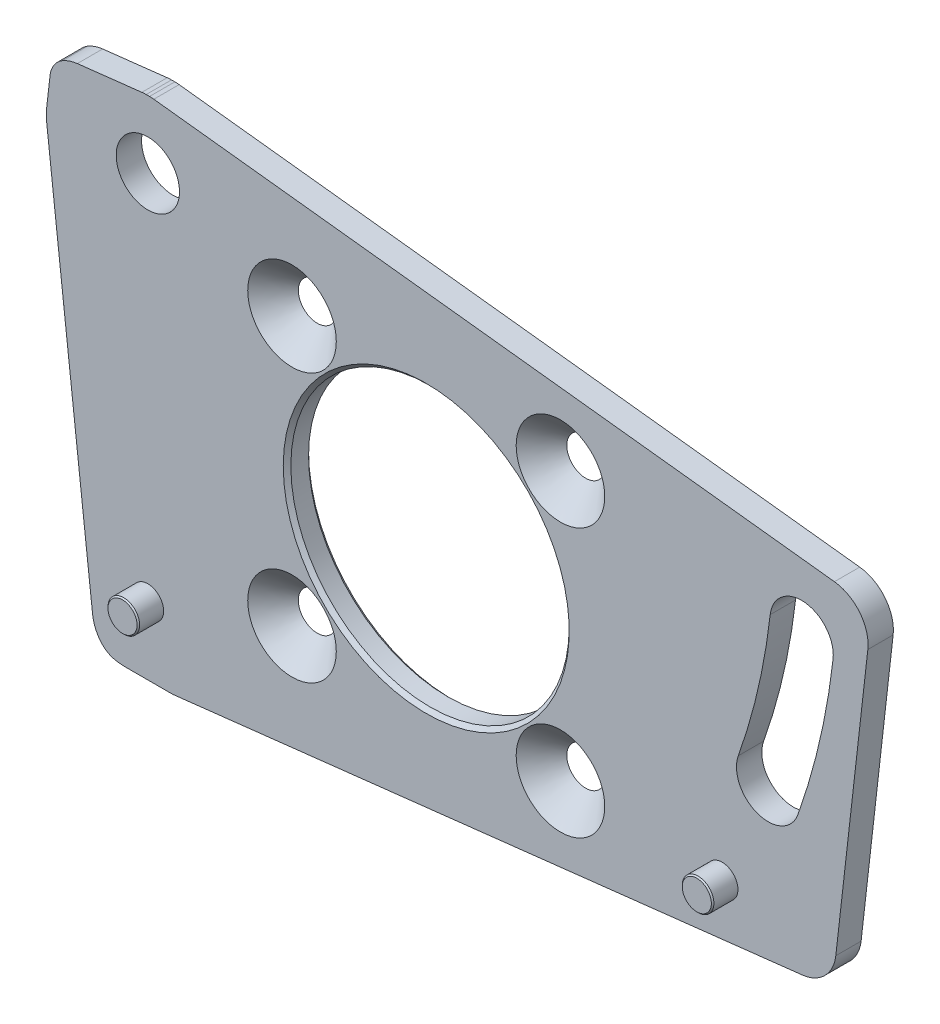
SolidWorks part; units mm, degrees
ref_plane "Płaszczyzna przednia" through (0, 0, 0) normal (0, 0, 1) x (1, 0, 0)
ref_plane "Płaszczyzna górna" through (0, 0, 0) normal (0, 1, 0) x (1, 0, 0)
ref_plane "Płaszczyzna prawa" through (0, 0, 0) normal (1, 0, 0) x (0, 0, -1)
sketch "Szkic1" plane through (0, 0, 0) normal (0, 0, 1) x (1, 0, 0)
  line L0 (0, 0) -> (-23.297, 23.297) construction
  line L1 (-27, -20) -> (27, -20)
  line L2 (-30, -17) -> (-30, 17)
  line L3 (-27, 20) -> (27, 20)
  line L4 (30, -17) -> (30, 17)
  line L5 (-30, -20) -> (30, 20) construction
  line L6 (-30, 20) -> (30, -20) construction
  line L7 (0, 0) -> (25.2349, 25.2349) construction
  arc A0 (27, 20) -> (30, 17) centre (27, 17) cw
  arc A1 (27, -20) -> (30, -17) centre (27, -17) ccw
  arc A2 (-27, -20) -> (-30, -17) centre (-27, -17) cw
  arc A3 (-30, 17) -> (-27, 20) centre (-27, 17) cw
  circle A4 centre (0, 0) radius 11
  circle A5 centre (-22, 14.6667) radius 2.5
  circle A8 centre (-10.6066, -10.6066) radius 1.5
  circle A9 centre (10.6066, -10.6066) radius 1.5
  circle A10 centre (10.6066, 10.6066) radius 1.5
  circle A11 centre (-10.6066, 10.6066) radius 1.5
  circle A12 centre (0, 0) radius 15 construction
  point P0 (0, 0)
  dimension "D3" = 3
  dimension "D4" = 30
  dimension "D6" = 3
  dimension "D7" = 3
  dimension "D8" = 3
  dimension "D9" = 3
  dimension "D10" = 22
  dimension "D11" = 5
  dimension "D1" = 60
  dimension "D2" = 40
  dimension "D5" = 45
  dimension "D12" = 8
extrude "Dodanie-wyciągnięcie1" add sketch "Szkic1" along normal blind 2
chamfer "Sfazowanie1" distance 0.3 angle 45 2 edges at (11, 0, 0) (11, 0, 2)
chamfer "Sfazowanie2" distance 2 angle 45 4 edges at (-9.1066, -10.6066, 2) (12.1066, -10.6066, 2) (12.1066, 10.6066, 2) (-9.1066, 10.6066, 2)
sketch "Szkic2" plane through (0, 0, 2) normal (0, 0, 1) x (1, 0, 0)
  line L9 (26.0813, 25.5127) -> (-27.5716, 19.3997)
  line L10 (-30.2127, 16.0794) -> (-26.3638, -17.7021)
  line L11 (-23.0435, -20.3432) -> (30.6094, -14.2302)
  line L12 (33.2505, -10.9099) -> (29.4016, 22.8716)
  arc A8 (29.4016, 22.8716) -> (26.0813, 25.5127) centre (26.4209, 22.532) ccw
  arc A9 (-27.5716, 19.3997) -> (-30.2127, 16.0794) centre (-27.232, 16.419) ccw
  arc A10 (-26.3638, -17.7021) -> (-23.0435, -20.3432) centre (-23.3831, -17.3625) ccw
  arc A11 (30.6094, -14.2302) -> (33.2505, -10.9099) centre (30.2698, -11.2495) ccw
sketch "Szkic3" plane through (0, 0, 0) normal (0, 0, 1) x (1, 0, 0)
  line L0 (-22, 14.6667) -> (-22, -14.6667) construction
  line L1 (25.8424, 10.5577) -> (-22, 14.6667) construction
  line L2 (-22, 14.6667) -> (23.383, -11.0277) construction
  line L3 (26, 16) -> (-22, 14.6667) construction
  line L4 (-22, 14.6667) -> (25.0697, 5.1682) construction
  line L5 (26, -5.725) -> (-22, 14.6667) construction
  line L6 (-22, 14.6667) -> (20.1826, -16) construction
  line L7 (-18.6794, -14.4781) -> (-22, 14.6667) construction
  line L8 (-22, 14.6667) -> (-25.3206, -14.4781) construction
  line L9 (-30, 17) -> (-30, -17) construction
  line L10 (-27, -20) -> (27, -20) construction
  line L11 (-27, -20) -> (27, -20) construction
  line L12 (30, -17) -> (30, 17) construction
  line L14 (27, 20) -> (-27, 20) construction
  line L15 (30, -17) -> (30, 17) construction
  circle A3 centre (-22, 14.6667) radius 29.3333 construction
  circle A4 centre (-22, 14.6667) radius 52.1519 construction
  arc A9 (-18.5379, -15.7201) -> (-18.8209, -13.2361) centre (-18.6794, -14.4781) ccw construction
  arc A10 (-25.4621, -15.7201) -> (-18.5379, -15.7201) centre (-22, 14.6667) ccw construction
  arc A11 (-25.1791, -13.2361) -> (-25.4621, -15.7201) centre (-25.3206, -14.4781) ccw construction
  arc A12 (-25.1791, -13.2361) -> (-18.8209, -13.2361) centre (-22, 14.6667) ccw construction
  circle A13 centre (-22, 14.6667) radius 48.0185 construction
  arc A18 (27.1505, -6.2137) -> (24.8495, -5.2362) centre (26, -5.725) ccw construction
  arc A19 (21.1937, -16.735) -> (27.1505, -6.2137) centre (-22, 14.6667) ccw construction
  arc A20 (19.1716, -15.265) -> (21.1937, -16.735) centre (20.1826, -16) ccw construction
  arc A21 (19.1716, -15.265) -> (24.8495, -5.2362) centre (-22, 14.6667) ccw construction
  circle A22 centre (-22, -14.6667) radius 1.25
  arc A27 (23.8444, 5.4154) -> (24.7505, 15.9653) centre (-22, 14.6667) ccw construction
  arc A28 (27.2495, 16.0347) -> (24.7505, 15.9653) centre (26, 16) ccw construction
  arc A29 (26.295, 4.9209) -> (27.2495, 16.0347) centre (-22, 14.6667) ccw construction
  arc A30 (23.8444, 5.4154) -> (26.295, 4.9209) centre (25.0697, 5.1682) ccw construction
  circle A31 centre (23.383, -11.0277) radius 1.25
  circle A32 centre (25.8424, 10.5577) radius 1.25
  dimension "D1" = 1.25
  dimension "D11" = 2.5
  dimension "D12" = 58.6667
  dimension "D13" = 104.3038
  dimension "D14" = 96.037
  dimension "D17" = 2.5
  dimension "D18" = 1.25
  dimension "D23" = 2.5
  dimension "D24" = 1.25
  dimension "D25" = 1.25
  dimension "D4" = 13
  dimension "D5" = 13
  dimension "D6" = 13
  dimension "D7" = 6.5
  dimension "D8" = 6.5
  dimension "D9" = 6.5
  dimension "D2" = 8
  dimension "D3" = 5.3333
  dimension "D10" = 13
  dimension "D15" = 4
  dimension "D16" = 4
  dimension "D19" = 13
  dimension "D20" = 13
  dimension "D21" = 4
  dimension "D22" = 4
extrude "Wytnij-wyciągnięcie1" [suppressed] cut sketch "Szkic3" along normal up to next
sketch "Szkic4" plane through (0, 0, 0) normal (0, 0, 1) x (1, 0, 0)
  line L4 (-30.8922, -19.2111) -> (22.7606, -25.3241)
  line L5 (-29.6844, 17.8906) -> (-33.5333, -15.8908)
  line L6 (27.2888, 14.4188) -> (-26.3641, 20.5317)
  line L7 (26.081, -22.683) -> (29.9299, 11.0984)
  arc A4 (-33.5333, -15.8908) -> (-30.8922, -19.2111) centre (-30.5526, -16.2304) ccw
  arc A5 (-26.3641, 20.5317) -> (-29.6844, 17.8906) centre (-26.7037, 17.551) ccw
  arc A6 (29.9299, 11.0984) -> (27.2888, 14.4188) centre (26.9492, 11.438) ccw
  arc A7 (22.7606, -25.3241) -> (26.081, -22.683) centre (23.1003, -22.3434) ccw
extrude "Wytnij-wyciągnięcie2" cut sketch "Szkic2" against normal through all flip side to cut
extrude "Wytnij-wyciągnięcie4" cut sketch "Szkic4" along normal through all flip side to cut
fillet "Zaokrąglenie2" radius 3 7 edges at (-20.0315, -20, 1) (-23.9685, -20, 1) (-21.6972, 20, 1) (-22.3028, 20, 1) (-30, 14.2124, 1) (-30, 15.1209, 1) (26.9972, -14.6418, 1)
fillet "Zaokrąglenie3" radius 2 2 edges at (-29.6268, 18.2259, 1) (-25.0131, -19.881, 1)
sketch "Szkic6" plane through (0, 0, 0) normal (0, 0, 1) x (1, 0, 0)
  line L0 (27.2888, 14.4188) -> (32.2566, 13.8527)
  line L1 (34.8977, 10.5324) -> (32.3658, -11.6899)
  line L2 (29.7247, -14.331) -> (24.6262, -14.9119)
  line L3 (-19.8622, -19.9807) -> (24.6262, -14.9119) construction
  line L4 (27.2888, 14.4188) -> (-21.5279, 19.9807) construction
  line L5 (24.6262, -14.9119) -> (27.2888, 14.4188)
  arc A0 (32.3658, -11.6899) -> (29.7247, -14.331) centre (29.3851, -11.3503) cw
  arc A1 (32.2566, 13.8527) -> (34.8977, 10.5324) centre (31.917, 10.872) cw
  point P14 (35.2373, 13.5131)
  dimension "D2" = 3
  dimension "D1" = 8
extrude "Dodanie-wyciągnięcie3" add sketch "Szkic6" along normal blind 2
sketch "Szkic5" plane through (0, 0, 0) normal (0, 0, 1) x (1, 0, 0)
  line L0 (0, 0) -> (3.4572, 30.3433) construction
  line L1 (32.2566, 13.8527) -> (-21.5279, 19.9807) construction
  line L2 (29.6657, 8.7801) -> (-22, 14.6667) construction
  line L3 (-22, 14.6667) -> (27.0174, -2.6913) construction
  circle A0 centre (-22, 14.6667) radius 2.5 construction
  circle A1 centre (-22, 14.6667) radius 2.5
  circle A2 centre (29.6657, 8.7801) radius 2.5 construction
  arc A3 (29.6657, 8.7801) -> (27.0174, -2.6913) centre (-22, 14.6667) cw construction
  arc A4 (29.374, -3.5258) -> (32.1497, 8.4971) centre (-22, 14.6667) ccw
  arc A5 (24.6608, -1.8568) -> (27.1818, 9.0631) centre (-22, 14.6667) ccw
  arc A6 (24.6608, -1.8568) -> (29.374, -3.5258) centre (27.0174, -2.6913) ccw
  arc A7 (32.1497, 8.4971) -> (27.1818, 9.0631) centre (29.6657, 8.7801) ccw
  point P2 (24.7354, 9.3418)
  point P11 (28.6672, 2.9692)
  point P18 (0, 0)
  dimension "D1" = 13
  dimension "D2" = 52
extrude "Wytnij-wyciągnięcie6" cut sketch "Szkic5" along normal through all contours A4 A7 A5 A6 region at (28.5044, 3.0068, 0)
extrude "Dodanie-wyciągnięcie2" add sketch "Szkic3<3>" along normal blind 4 contours A22 | A31 region at (-22, -14.6667, 0) region at (23.383, -11.0277, 0)
sketch "Szkic3<3>" plane through (0, 0, 0) normal (0, 0, 1) x (1, 0, 0) same geometry as "Szkic3"
chamfer "Sfazowanie3" distance 0.1 angle 45 2 edges at (24.633, -11.0277, 4) (-20.75, -14.6667, 4)
equation "\"D7@Szkic1\"=\"D6@Szkic1\""
equation "\"D8@Szkic1\"=\"D6@Szkic1\""
equation "\"D9@Szkic1\"=\"D6@Szkic1\""
equation "\"D7@Szkic3\"=\"D4@Szkic3\"/2"
equation "\"D8@Szkic3\"=\"D5@Szkic3\"/2"
equation "\"D9@Szkic3\"=\"D6@Szkic3\"/2"
equation "\"D25@Szkic3\"=\"D24@Szkic3\""
